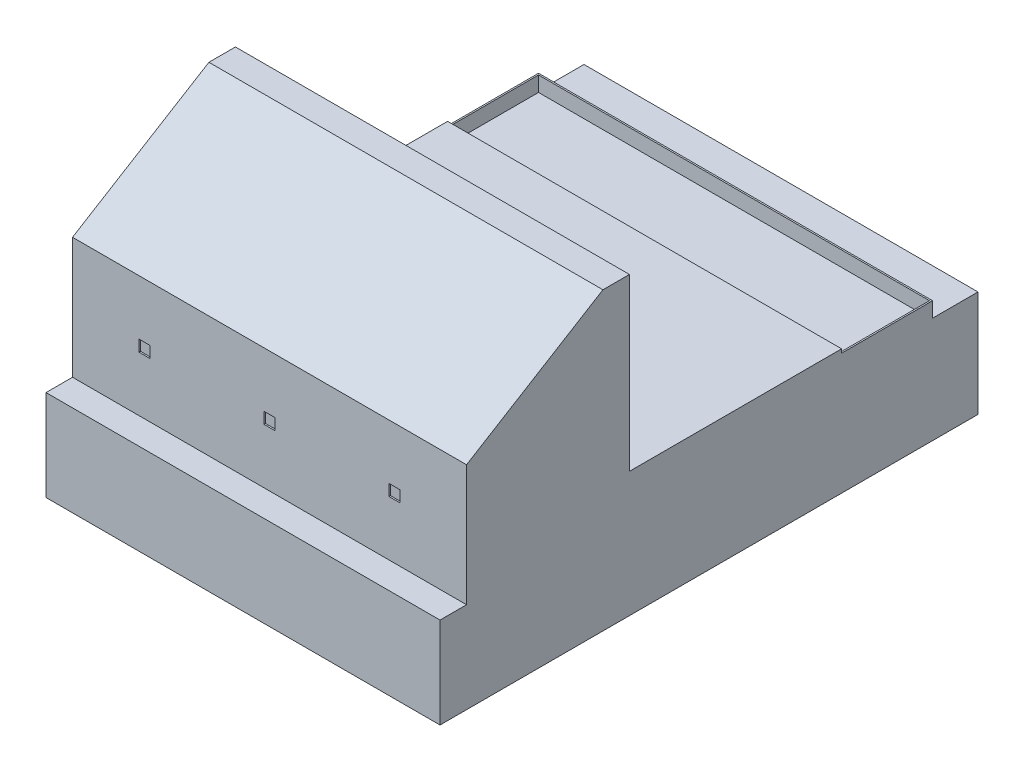
SolidWorks part; units mm, degrees
material "Ductile Iron (SN)"
ref_plane "Front Plane" through (0, 0, 0) normal (0, 0, 1) x (1, 0, 0)
ref_plane "Top Plane" through (0, 0, 0) normal (0, 1, 0) x (1, 0, 0)
ref_plane "Right Plane" through (0, 0, 0) normal (1, 0, 0) x (0, 0, -1)
sketch "Sketch2" plane through (0, 0, 0) normal (1, 0, 0) x (0, 0, -1)
  line L0 (0, 0) -> (0, 120)
  line L5 (0, 120) -> (35, 120)
  line L6 (35, 120) -> (35, 280)
  line L7 (35, 280) -> (215, 390)
  line L8 (215, 390) -> (250, 390)
  line L9 (250, 390) -> (250, 165)
  line L10 (250, 165) -> (530, 165)
  line L11 (530, 165) -> (530, 140)
  line L12 (530, 140) -> (710, 140)
  line L13 (710, 140) -> (710, 0)
  line L14 (710, 0) -> (0, 0)
  dimension "D1" = 140
  dimension "D2" = 165
  dimension "D3" = 120
  dimension "D4" = 280
  dimension "D5" = 35
  dimension "D6" = 710
  dimension "D7" = 280
  dimension "D8" = 35
  dimension "D9" = 215
  dimension "D10" = 390
extrude "Boss-Extrude2" add sketch "Sketch2" along normal blind 520
sketch "Sketch3" plane through (0, 0, 0) normal (0, -1, 0) x (1, 0, 0)
  line L0 (520, 0) -> (0, 0) construction
  line L1 (2, -2) -> (518, -2)
  line L2 (2, -2) -> (2, -708)
  line L3 (2, -708) -> (518, -708)
  line L4 (518, -2) -> (518, -708)
  line L5 (0, 0) -> (0, -710) construction
  line L6 (520, -710) -> (0, -710) construction
  line L7 (520, 0) -> (520, -710) construction
  line L12 (520, -710) -> (0, -710)
  line L13 (520, 0) -> (520, -710)
  line L14 (0, 0) -> (0, -710)
  line L15 (520, 0) -> (0, 0)
  dimension "D1" = 2
  dimension "D2" = 2
  dimension "D3" = 2
  dimension "D4" = 2
sketch "Sketch4" plane through (0, 0, -250) normal (0, 0, -1) x (-1, 0, 0)
  line L1 (-520, 165) -> (0, 165) construction
  line L5 (-515, 165) -> (-5, 165)
  line L8 (-520, 165) -> (0, 165) construction
  line L9 (-515, 385) -> (-5, 385)
  line L10 (-515, 385) -> (-515, 165)
  line L12 (-5, 385) -> (-5, 165)
  line L13 (-520, 390) -> (0, 390) construction
  line L14 (-520, 165) -> (-520, 390) construction
  line L15 (0, 165) -> (0, 390) construction
  dimension "D1" = 5
  dimension "D2" = 5
  dimension "D3" = 5
sketch "Sketch5" plane through (0, 188.2921, 115.0674) normal (0, 0.8533, 0.5215) x (1, 0, 0)
  line L0 (260, 386.8211) -> (260, 175.8709) construction
  line L1 (520, 386.8211) -> (0, 386.8211) construction
  line L2 (520, 175.8709) -> (0, 175.8709) construction
  line L4 (180, 316.346) -> (340, 316.346)
  line L5 (180, 316.346) -> (180, 246.346)
  line L6 (180, 246.346) -> (340, 246.346)
  line L7 (340, 316.346) -> (340, 246.346)
  line L8 (180, 316.346) -> (340, 246.346) construction
  line L9 (180, 246.346) -> (340, 316.346) construction
  circle A0 centre (420, 281.346) radius 15
  circle A1 centre (100, 281.346) radius 15
  circle A2 centre (50, 281.346) radius 15
  point P6 (260, 281.346)
  dimension "D3" = 30
  dimension "D4" = 30
  dimension "D5" = 30
  dimension "D1" = 70
  dimension "D2" = 160
  dimension "D6" = 160
  dimension "D7" = 50
  dimension "D8" = 160
sketch "Sketch6" plane through (0, 0, -35) normal (0, 0, 1) x (1, 0, 0)
  line L0 (260, 280) -> (260, 120) construction
  line L1 (520, 280) -> (0, 280) construction
  line L2 (520, 120) -> (0, 120) construction
  line L3 (0, 200) -> (520, 200) construction
  line L4 (0, 280) -> (0, 120) construction
  line L5 (520, 280) -> (520, 120) construction
  line L7 (252.5, 207.5) -> (267.5, 207.5)
  line L8 (252.5, 207.5) -> (252.5, 192.5)
  line L9 (252.5, 192.5) -> (267.5, 192.5)
  line L10 (267.5, 207.5) -> (267.5, 192.5)
  line L11 (252.5, 207.5) -> (267.5, 192.5) construction
  line L12 (252.5, 192.5) -> (267.5, 207.5) construction
  line L13 (87.5, 207.5) -> (102.5, 207.5)
  line L14 (87.5, 207.5) -> (87.5, 192.5)
  line L15 (87.5, 192.5) -> (102.5, 192.5)
  line L16 (102.5, 207.5) -> (102.5, 192.5)
  line L17 (87.5, 207.5) -> (102.5, 192.5) construction
  line L18 (87.5, 192.5) -> (102.5, 207.5) construction
  line L19 (417.5, 207.5) -> (432.5, 207.5)
  line L20 (417.5, 207.5) -> (417.5, 192.5)
  line L21 (417.5, 192.5) -> (432.5, 192.5)
  line L22 (432.5, 207.5) -> (432.5, 192.5)
  line L23 (417.5, 207.5) -> (432.5, 192.5) construction
  line L24 (417.5, 192.5) -> (432.5, 207.5) construction
  point P12 (260, 200)
  point P17 (95, 200)
  point P22 (425, 200)
  dimension "D1" = 15
  dimension "D2" = 15
  dimension "D3" = 15
  dimension "D4" = 15
  dimension "D5" = 15
  dimension "D6" = 15
  dimension "D7" = 330
  dimension "D8" = 165
extrude "Cut-Extrude6" cut sketch "Sketch6" against normal blind 2
shell "Shell1" thickness 2 removed face at (260, 277.5, -250)
sketch "Sketch7" plane through (0, 140, 0) normal (0, 1, 0) x (1, 0, 0)
  line L0 (0, 0) -> (0, 710) construction
  line L1 (520, 530) -> (0, 530)
  line L2 (520, 530) -> (520, 650)
  line L3 (520, 650) -> (0, 650)
  line L4 (0, 530) -> (0, 650)
  point P6 (0, 710)
  point P7 (0, 672.8174)
  dimension "D1" = 120
extrude "Boss-Extrude3" add sketch "Sketch7" along normal blind 20
shell "Shell2" thickness 2 removed face at (260, 160, -590)
